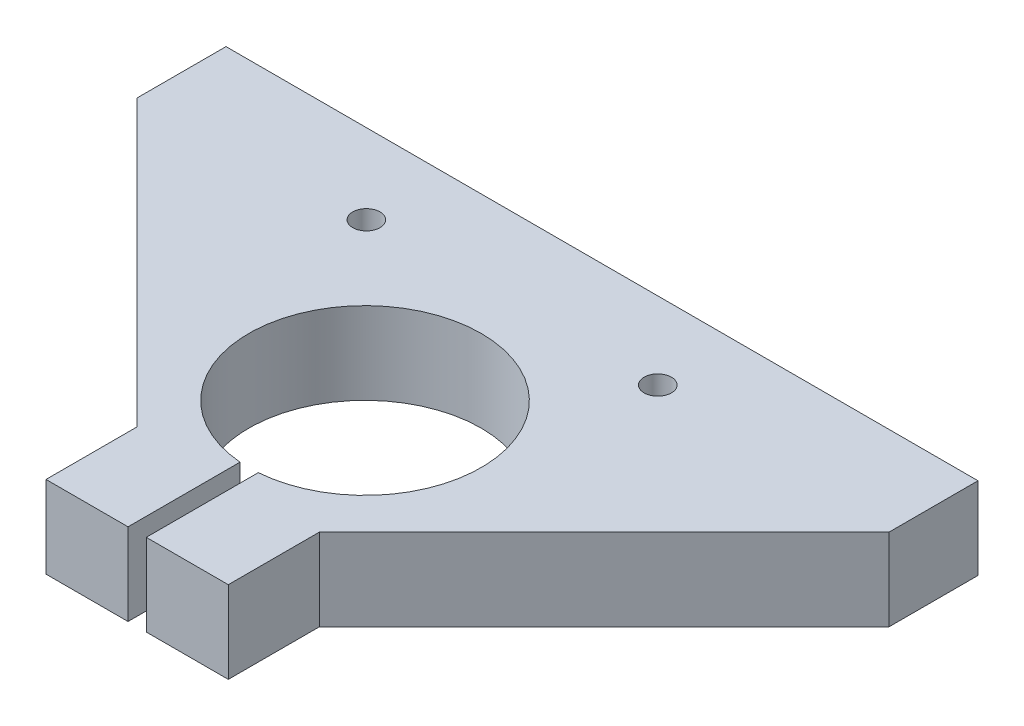
SolidWorks part; units mm, degrees
material "ABS"
ref_plane "Front Plane" through (0, 0, 0) normal (0, 0, 1) x (1, 0, 0)
ref_plane "Top Plane" through (0, 0, 0) normal (0, 1, 0) x (1, 0, 0)
ref_plane "Right Plane" through (0, 0, 0) normal (1, 0, 0) x (0, 0, -1)
sketch "Sketch1" plane through (0, 0, 0) normal (0, 1, 0) x (1, 0, 0)
  line L0 (-83.1248, -7.7737) -> (-20.6248, -70.2737)
  line L2 (-83.1248, 11.7263) -> (-83.1248, -7.7737)
  line L3 (-2.6248, -90.2737) -> (-2.6248, -65.6951)
  line L4 (81.8752, 11.7263) -> (81.8752, -7.7737)
  line L5 (19.3752, -70.2737) -> (81.8752, -7.7737)
  line L6 (1.3752, -90.2737) -> (1.3752, -65.6951)
  line L7 (-83.1248, 11.7263) -> (81.8752, 11.7263)
  line L8 (-83.1248, 11.7263) -> (81.8752, 11.7263) construction
  line L11 (-20.6248, -70.2737) -> (-20.6248, -90.2737)
  line L12 (-20.6248, -90.2737) -> (-2.6248, -90.2737)
  line L16 (1.3752, -90.2737) -> (19.3752, -90.2737)
  line L17 (19.3752, -70.2737) -> (19.3752, -90.2737)
  arc A0 (1.3752, -65.6951) -> (-2.6248, -65.6951) centre (-0.6248, -40.2737) ccw
  dimension "D5" = 102
  dimension "D7" = 135
  dimension "D8" = 135
  dimension "D1" = 20
extrude "Extrude1" add sketch "Sketch1" along normal blind 18
hole_wizard "Ø6.0 (6) Diameter Hole1" positions "3DSketch1" profile "Sketch2" hole size "Ø6.0" standard "ISO" end condition through all
sketch3d "3DSketch1"
  point P0 (-34.8169, 18, 5.7856)
  point P2 (28.5542, 18, 5.2164)
sketch "Sketch2" plane through (-34.8169, 18, 5.7856) normal (1, 0, 0) x (0, 0, 1)
  line L0 (0, 0) -> (0, 18)
  line L1 (0, 18) -> (3, 18)
  line L2 (3, 18) -> (3, 0)
  line L5 (3, 0) -> (0, 0)
  line L11 (0, -6.35) -> (0, 107.95) construction
  dimension "Thru Hole Dia." = 6
  dimension "Thru Hole Depth" = 18
ref_axis "Axis1" through (-0.6248, 18, -11.7263) along (0, 0, 1)
ref_plane "Plane1" through (-0.6248, 0, 0) normal (1, 0, 0) x (0, 0, -1)
equation "\"D8@Sketch1\"=\"D7@Sketch1\""
